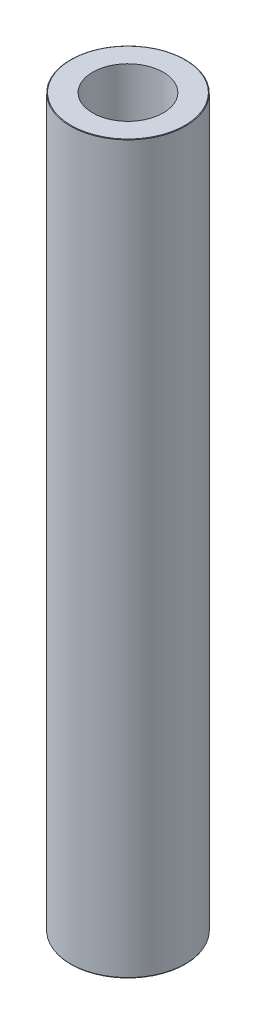
SolidWorks part; units mm, degrees
ref_plane "Front Plane" through (0, 0, 0) normal (0, 0, 1) x (1, 0, 0)
ref_plane "Top Plane" through (0, 0, 0) normal (0, 1, 0) x (1, 0, 0)
ref_plane "Right Plane" through (0, 0, 0) normal (1, 0, 0) x (0, 0, -1)
sketch "Sketch1" plane through (0, 0, 0) normal (0, 1, 0) x (1, 0, 0)
  circle A0 centre (0, 0) radius 47.5
  dimension "SHAFT_OD" = 95
extrude "Boss-Extrude1" add sketch "Sketch1" along normal blind 600
sketch "Sketch2" plane through (0, 0, 0) normal (0, 1, 0) x (1, 0, 0)
  circle A0 centre (0, 0) radius 29.1577
  dimension "BORE_D" = 58.3155
extrude "Cut-Extrude1" cut sketch "Sketch2" along normal through all
chamfer "Chamfer1" distance 0.2864 angle 60.631 2 edges at (0, 600, 47.5) (0, 0, 47.5) first distance on face at (0, 600, 47.5) first distance on face at (0, 0, 29.1577)
